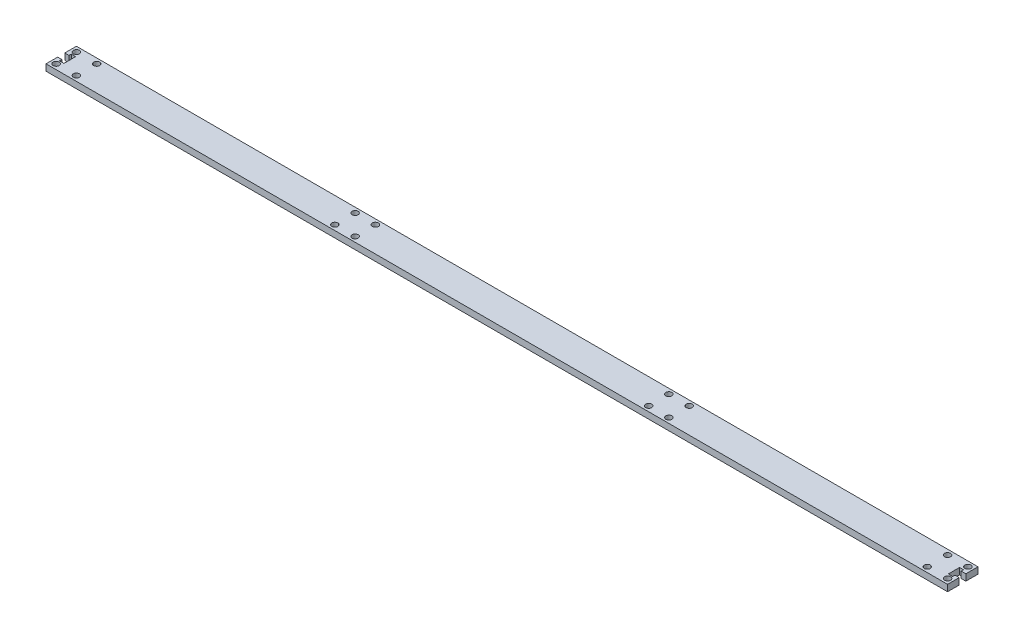
SolidWorks part; units mm, degrees
ref_plane "Front Plane" through (0, 0, 0) normal (0, 0, 1) x (1, 0, 0)
ref_plane "Top Plane" through (0, 0, 0) normal (0, 1, 0) x (1, 0, 0)
ref_plane "Right Plane" through (0, 0, 0) normal (1, 0, 0) x (0, 0, -1)
sketch "Sketch1" plane through (0, 0, 0) normal (0, 1, 0) x (1, 0, 0)
  line L0 (152.4, 7.5) -> (144.9, 7.5)
  line L1 (0, 0) -> (152.4, 0)
  line L2 (0, 0) -> (0, 15)
  line L3 (0, 15) -> (152.4, 15)
  line L4 (152.4, 0) -> (152.4, 15)
  line L5 (0, 7.5) -> (7.5, 7.5)
  line L6 (7.5, 7.5) -> (7.5, 12.5)
  line L7 (7.5, 12.5) -> (2.5, 12.5)
  line L8 (7.5, 12.5) -> (12.5, 12.5)
  line L9 (7.5, 7.5) -> (7.5, 2.5)
  line L10 (7.5, 2.5) -> (2.5, 2.5)
  line L11 (7.5, 2.5) -> (12.5, 2.5)
  line L12 (76.2, 0) -> (76.2, 15)
  line L13 (152.4, 0) -> (152.4, 15)
  line L14 (152.4, 0) -> (292.1, 0)
  line L15 (152.4, 15) -> (292.1, 15)
  line L16 (222.25, 0) -> (222.25, 15)
  line L17 (292.1, 0) -> (292.1, 15)
  line L18 (444.5, 15) -> (292.1, 15)
  line L19 (292.1, 0) -> (292.1, 15)
  line L20 (444.5, 0) -> (292.1, 0)
  line L21 (444.5, 0) -> (444.5, 15)
  circle A0 centre (2.5, 2.5) radius 1.5
  circle A1 centre (2.5, 12.5) radius 1.5
  circle A2 centre (12.5, 12.5) radius 1.5
  circle A3 centre (12.5, 2.5) radius 1.5
  circle A4 centre (149.9, 12.5) radius 1.5
  circle A5 centre (139.9, 12.5) radius 1.5
  circle A6 centre (149.9, 2.5) radius 1.5
  circle A7 centre (139.9, 2.5) radius 1.5
  circle A8 centre (432, 12.5) radius 1.5
  circle A9 centre (442, 12.5) radius 1.5
  circle A10 centre (442, 2.5) radius 1.5
  circle A11 centre (432, 2.5) radius 1.5
  circle A12 centre (294.6, 12.5) radius 1.5
  circle A13 centre (304.6, 12.5) radius 1.5
  circle A14 centre (304.6, 2.5) radius 1.5
  circle A15 centre (294.6, 2.5) radius 1.5
  dimension "D11" = 69.85
  dimension "D1" = 15
  dimension "D2" = 152.4
  dimension "D3" = 7.5
  dimension "D4" = 7.5
  dimension "D5" = 5
  dimension "D6" = 5
  dimension "D7" = 5
  dimension "D8" = 5
  dimension "D9" = 5
  dimension "D10" = 5
extrude "Boss-Extrude1" add sketch "Sketch1" along normal blind 3.175 contours A3 A0 L2 L1 L12 L3 A1 A2 | L12 L1 L4 L3 A6 A4 A5 A7 | L14 L16 L15 L4 | L14 L17 L15 L16 | L20 L21 L18 L17 A15 A14 A13 A12 A10 A8 A9 A11 region at (38.8762, 0, -7.5) region at (113.5238, 0, -7.5) region at (187.325, 0, -7.5) region at (257.175, 0, -7.5) region at (368.3, 0, -7.5)
sketch "Sketch4" plane through (0, 3.175, 0) normal (0, 1, 0) x (1, 0, 0)
  line L0 (444.5, 7.5) -> (432.4339, 7.5)
  line L1 (444.5, 0) -> (444.5, 15) construction
  line L2 (0, 15) -> (444.5, 15) construction
  line L3 (222.25, 15) -> (222.25, 0)
  line L4 (0, 0) -> (444.5, 0) construction
  line L5 (444.5, 9) -> (442.2, 9)
  line L6 (442.2, 9) -> (442.2, 10.15)
  line L7 (442.2, 10.15) -> (440.5, 10.15)
  line L8 (440.5, 10.15) -> (440.5, 7.5)
  line L9 (444.5, 9.25) -> (442.45, 9.25)
  line L10 (442.45, 9.25) -> (442.45, 10.4)
  line L11 (442.45, 10.4) -> (440.25, 10.4)
  line L12 (440.25, 10.4) -> (440.25, 7.5)
  line L13 (444.5, 5.75) -> (442.45, 5.75)
  line L14 (442.45, 5.75) -> (442.45, 4.6)
  line L15 (442.45, 4.6) -> (440.25, 4.6)
  line L16 (440.25, 4.6) -> (440.25, 7.5)
  line L17 (0, 9.25) -> (2.05, 9.25)
  line L18 (2.05, 9.25) -> (2.05, 10.4)
  line L19 (0, 5.75) -> (2.05, 5.75)
  line L20 (2.05, 5.75) -> (2.05, 4.6)
  line L21 (2.05, 4.6) -> (4.25, 4.6)
  line L22 (4.25, 4.6) -> (4.25, 7.5)
  line L23 (4.25, 10.4) -> (4.25, 7.5)
  line L24 (2.05, 10.4) -> (4.25, 10.4)
  line L25 (0, 9.25) -> (0, 5.75)
  line L26 (444.5, 9.25) -> (444.5, 5.75)
  line M20 (0, 15) -> (0, 0)
  line M22 (444.5, 0) -> (444.5, 15)
  dimension "D1" = 1.5
  dimension "D2" = 1.15
  dimension "D3" = 1.7
  dimension "D4" = 2.65
  dimension "D5" = 2.3
  dimension "D6" = 0.25
extrude "Cut-Extrude2" cut sketch "Sketch4" against normal blind 10 contours L16 L15 L14 L13 L0 M22 | L7 L8 L0 L5 L6 M22 | L24 L18 L17 L19 L20 L21 L22 L23 M20 region at (442.1148, 3.175, -6.257) region at (442.2174, 3.175, -8.5756) region at (2.3852, 3.175, -7.5)
sketch "Sketch6" plane through (440.5, 0, 0) normal (1, 0, 0) x (0, 0, -1)
  line L0 (10.15, 0) -> (7.5, 0) construction
  line L5 (7.5, 3.175) -> (10.15, 3.175)
  line L6 (7.5, 3.175) -> (7.5, 0)
  line L7 (7.5, 0) -> (10.15, 0)
  line L8 (10.15, 3.175) -> (10.15, 0)
extrude "Cut-Extrude3" cut sketch "Sketch6" against normal blind 0.25
